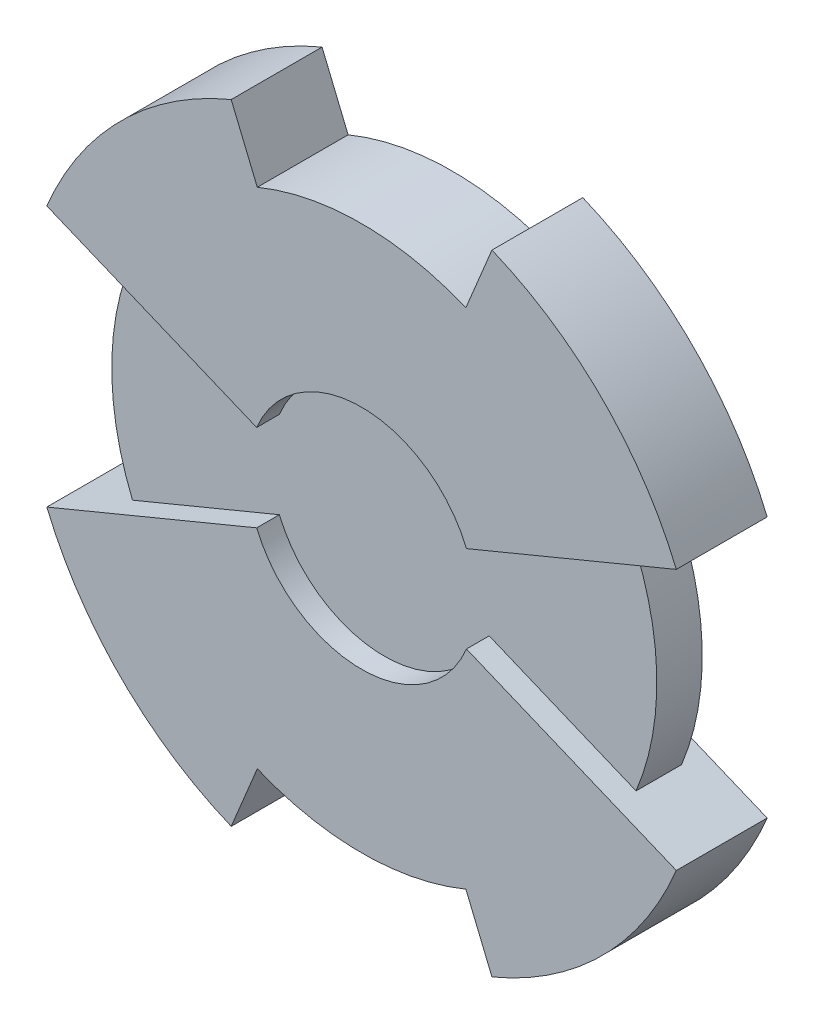
SolidWorks part; units mm, degrees
ref_plane "Front Plane" through (0, 0, 0) normal (0, 0, 1) x (1, 0, 0)
ref_plane "Top Plane" through (0, 0, 0) normal (0, 1, 0) x (1, 0, 0)
ref_plane "Right Plane" through (0, 0, 0) normal (1, 0, 0) x (0, 0, -1)
sketch "Sketch1" plane through (0, 0, 0) normal (0, 0, 1) x (1, 0, 0)
  line L0 (23.097, -9.5671) -> (69.291, -28.7013)
  line L1 (23.097, 9.5671) -> (69.291, 28.7013)
  line L2 (-75, 0) -> (75, 0) construction
  line L3 (0, 85.1107) -> (0, -105.4999) construction
  line L4 (-23.097, -9.5671) -> (-69.291, -28.7013)
  line L5 (-23.097, 9.5671) -> (-69.291, 28.7013)
  line L6 (-22.961, 55.4328) -> (-28.7013, 69.291)
  line L7 (22.961, 55.4328) -> (28.7013, 69.291)
  line L8 (22.961, -55.4328) -> (28.7013, -69.291)
  line L9 (-22.961, -55.4328) -> (-28.7013, -69.291)
  arc A0 (-28.7013, 69.291) -> (-28.7013, -69.291) centre (0, 0) ccw
  circle A1 centre (0, 0) radius 60
  arc A2 (23.097, 9.5671) -> (-23.097, 9.5671) centre (0, 0) ccw
  arc A3 (-23.097, -9.5671) -> (23.097, -9.5671) centre (0, 0) ccw
  arc A4 (28.7013, -69.291) -> (28.7013, 69.291) centre (0, 0) ccw
  dimension "D1" = 150
  dimension "D2" = 120
  dimension "D3" = 50
  dimension "D4" = 22.5
  dimension "D5" = 22.5
  dimension "D6" = 22.5
extrude "Boss-Extrude1" add sketch "Sketch1" along normal mid plane 20 contours A2 L1 A1 L5 | A1 L6 A0 L5 | L1 A4 L7 A1 | A1 L4 A0 L9 | A3 L4 A1 L0 | L8 A4 L0 A1 region at (0, -35.2127, 0) region at (46.7038, -46.7038, 0) region at (-46.7038, -46.7038, 0) region at (46.7038, 46.7038, 0) region at (0, 35.2127, 0) region at (-46.7038, 46.7038, 0)
extrude "Boss-Extrude2" add sketch "Sketch1<3>" along normal mid plane 10 contours L4 A3 L0 A1 L1 A2 L5 region at (0, 0, 0)
sketch "Sketch1<3>" plane through (0, 0, 0) normal (0, 0, 1) x (1, 0, 0) same geometry as "Sketch1"
